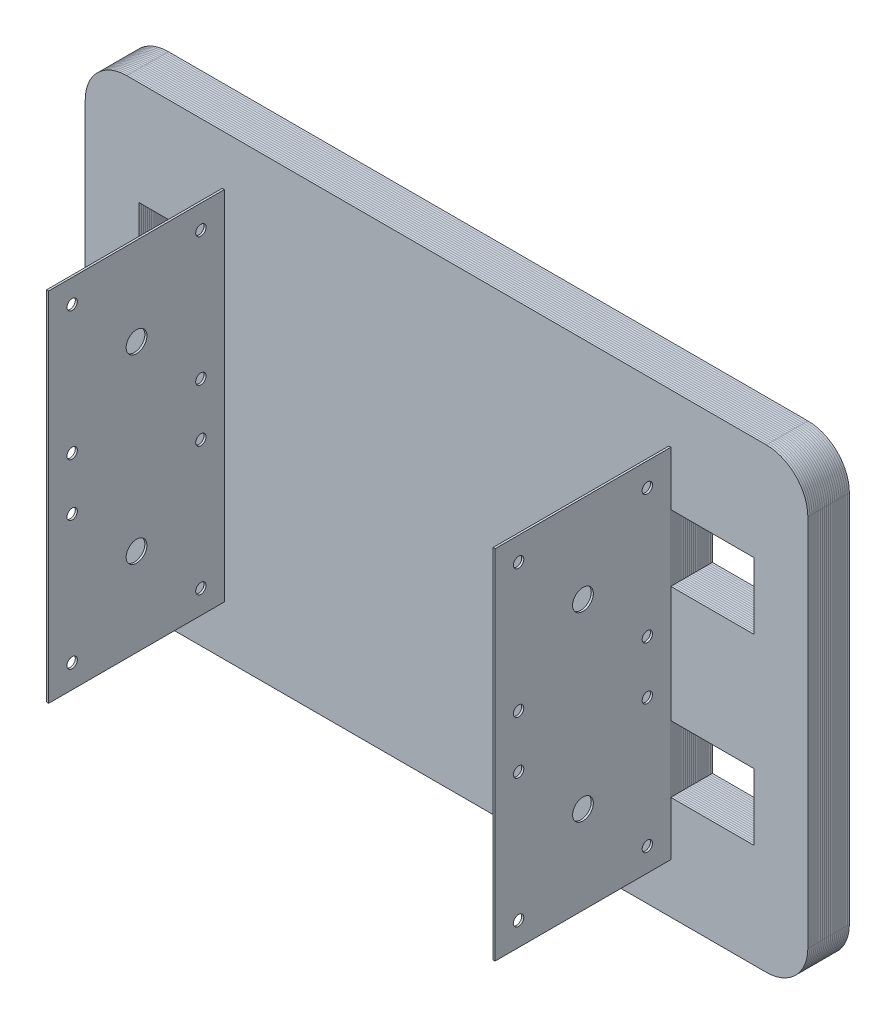
SolidWorks part; units mm, degrees
other "Item de detalhe5"
other "Item de detalhe6"
other "Item de detalhe8"
other "Pasta de soldas"
other "Cordão de solda...1"
other "Cordão de solda...2"
other "Cordão de solda...4"
other "Marcação1"
sketch "Esboço44" plane through (-174, 0, -8.5) normal (-1, 0, 0) x (0, 0, 1)
material "AISI 304"
ref_plane "Plano frontal" through (0, 0, 0) normal (0, 0, 1) x (1, 0, 0)
ref_plane "Plano superior" through (0, 0, 0) normal (0, 1, 0) x (1, 0, 0)
ref_plane "Plano direito" through (0, 0, 0) normal (1, 0, 0) x (0, 0, -1)
sketch "Esboço2" plane through (0, 0, 0) normal (0, 0, 1) x (1, 0, 0)
  line L22 (-10, 0) -> (-164, 0)
  line L23 (0, 10) -> (0, 100)
  line L24 (-10, 110) -> (-164, 110)
  line L25 (-174, 10) -> (-174, 100)
  line L26 (-33.5, 98) -> (-33, 98)
  line L27 (-161, 85) -> (-141, 85)
  line L28 (-161, 85) -> (-161, 69)
  line L29 (-161, 69) -> (-141, 69)
  line L30 (-141, 85) -> (-141, 69)
  line L31 (-33, 85) -> (-13, 85)
  line L32 (-33, 85) -> (-33, 69)
  line L33 (-33, 69) -> (-13, 69)
  line L34 (-13, 85) -> (-13, 69)
  line L35 (-161, 41) -> (-141, 41)
  line L36 (-161, 41) -> (-161, 25)
  line L37 (-161, 25) -> (-141, 25)
  line L38 (-141, 41) -> (-141, 25)
  line L39 (-33, 41) -> (-13, 41)
  line L40 (-33, 41) -> (-33, 25)
  line L41 (-33, 25) -> (-13, 25)
  line L42 (-13, 41) -> (-13, 25)
  line L50 (-140.5, 12) -> (-141, 12)
  line L54 (-33, 12) -> (-33.5, 12)
  line L55 (-33, 12) -> (-33, 98)
  line L59 (-140.5, 98) -> (-140.5, 12)
  line L60 (-33.5, 98) -> (-33.5, 12)
  line L61 (-140.5, 98) -> (-141, 98)
  line L62 (-141, 98) -> (-141, 12)
  arc A4 (-164, 0) -> (-174, 10) centre (-164, 10) cw
  arc A5 (-10, 0) -> (0, 10) centre (-10, 10) ccw
  arc A6 (0, 100) -> (-10, 110) centre (-10, 100) ccw
  arc A7 (-164, 110) -> (-174, 100) centre (-164, 100) ccw
  point P7 (-174, 0)
  point P10 (0, 0)
  point P13 (0, 110)
  point P16 (-174, 110)
  point P37 (-33, 55)
  dimension "D3" = 10
  dimension "D1" = 110
  dimension "D2" = 174
  dimension "D4" = 20
  dimension "D5" = 16
  dimension "D6" = 13
  dimension "D7" = 25
  dimension "D8" = 13
  dimension "D9" = 25
  dimension "D10" = 86
  dimension "D11" = 0.5
  dimension "D12" = 14
extrude "Ressalto-extrusão8" add sketch "Esboço2" against normal blind 0.5 contours L24 A7 L25 A4 L22 A5 L23 A6 L54 L40 L39 L42 L41 L61 L30 L29 L28 L27 L26 L32 L31 L34 L33 L50 L38 L37 L36 L35 | L61 L30 | L38 L50 | L32 L26 | L54 L40 region at (-87, 55, 0) region at (-33.25, 55, 0) region at (-140.75, 55, 0)
extrude "Ressalto-extrusão9" add sketch "Esboço2<13>" along normal blind 42.3 separate body contours L61 L62 L30 L38 L50 L59 | L26 L60 L54 L55 L40 L32 region at (-33.25, 55, 0) region at (-140.75, 55, 0)
sketch "Esboço2<13>" plane through (0, 0, 0) normal (0, 0, 1) x (1, 0, 0) same geometry as "Esboço2"
hole_wizard "Broca de rosquear para tarraxa de M3x0.51" positions "Esboço25" profile "Esboço26" hole size "M3x0.5" standard "Ansi Metric"
sketch "Esboço25" plane through (-141, 0, 0) normal (-1, 0, 0) x (0, 0, 1)
  line L0 (42.3, 98) -> (0, 98) construction
  line L1 (42.3, 98) -> (42.3, 12) construction
  line L2 (42.3, 12) -> (0, 12) construction
  point P0 (36.65, 92.35)
  point P2 (5.65, 92.35)
  point P4 (5.65, 61.35)
  point P6 (36.65, 61.35)
  point P8 (5.65, 48.65)
  point P10 (36.65, 48.65)
  point P12 (36.65, 17.65)
  point P14 (5.65, 17.65)
  dimension "D1" = 31
  dimension "D2" = 31
  dimension "D3" = 5.65
  dimension "D4" = 5.65
  dimension "D5" = 5.65
  dimension "D6" = 31
sketch "Esboço26" plane through (-141, 92.35, 36.65) normal (0, 1, 0) x (0, 0, 1)
  line L0 (0, 0) -> (0, 25.4)
  line L1 (0, 25.4) -> (1.25, 24.6489)
  line L2 (1.25, 24.6489) -> (1.25, 0)
  line L5 (1.25, 0) -> (0, 0)
  line L10 (0, 25.4) -> (-1.25, 24.6489) construction
  line L11 (0, -6.35) -> (0, 107.95) construction
  dimension "Hole Dia." = 2.5
  dimension "Hole Depth" = 25.4
  dimension "Drill Angle" = 118
sketch "Esboço27" plane through (-141, 0, 0) normal (-1, 0, 0) x (0, 0, 1)
  circle A0 centre (5.65, 92.35) radius 1.25
  circle A1 centre (36.65, 92.35) radius 1.25
  circle A2 centre (5.65, 61.35) radius 1.25
  circle A3 centre (36.65, 61.35) radius 1.25
  circle A4 centre (5.65, 48.65) radius 1.25
  circle A5 centre (36.65, 48.65) radius 1.25
  circle A6 centre (5.65, 17.65) radius 1.25
  circle A7 centre (36.65, 17.65) radius 1.25
  circle A8 centre (21.15, 76.85) radius 2.5
  circle A9 centre (21.15, 33.15) radius 2.5
  dimension "D1" = 5
  dimension "D2" = 15.5
  dimension "D3" = 15.5
  dimension "32/2" = 15.5
  dimension "D4" = 15.5
extrude "Corte-extrusão2" cut sketch "Esboço27" against normal through all both and the other way through all
extrude "Corte-extrusão3" cut sketch "Esboço27<2>" against normal through all both and the other way through all
sketch "Esboço27<2>" plane through (-141, 0, 0) normal (-1, 0, 0) x (0, 0, 1) same geometry as "Esboço27"
sketch "Esboço28" plane through (0, 0, -0.5) normal (0, 0, -1) x (-1, 0, 0)
  line L0 (10, 110) -> (164, 110)
  line L1 (174, 100) -> (174, 10)
  line L2 (164, 0) -> (10, 0)
  line L3 (10, 0) -> (164, 0) construction
  line L4 (0, 10) -> (0, 100)
  line L5 (161, 41) -> (161, 25) construction
  line L6 (13, 85) -> (33, 85)
  line L7 (13, 85) -> (13, 69)
  line L8 (13, 69) -> (33, 69)
  line L9 (33, 85) -> (33, 69)
  line L10 (13, 41) -> (33, 41)
  line L11 (13, 41) -> (13, 25)
  line L12 (13, 25) -> (33, 25)
  line L13 (33, 41) -> (33, 25)
  line L14 (141, 85) -> (161, 85)
  line L15 (141, 85) -> (141, 69)
  line L16 (141, 69) -> (161, 69)
  line L17 (161, 85) -> (161, 69)
  line L18 (141, 41) -> (161, 41)
  line L19 (141, 41) -> (141, 25)
  line L20 (141, 25) -> (161, 25)
  line L21 (161, 41) -> (161, 25)
  arc A0 (164, 0) -> (174, 10) centre (164, 10) ccw construction
  arc A1 (0, 100) -> (10, 110) centre (10, 100) cw
  arc A2 (10, 110) -> (0, 100) centre (10, 100) ccw construction
  arc A3 (164, 110) -> (174, 100) centre (164, 100) cw
  arc A4 (174, 100) -> (164, 110) centre (164, 100) ccw construction
  arc A5 (10, 0) -> (0, 10) centre (10, 10) cw
  arc A7 (174, 10) -> (164, 0) centre (164, 10) cw
  arc A8 (0, 10) -> (10, 0) centre (10, 10) ccw construction
extrude "Ressalto-extrusão10" add sketch "Esboço28" along normal blind 0.5 separate body
sketch "Esboço29" plane through (0, 0, -1) normal (0, 0, -1) x (-1, 0, 0)
  line L0 (10, 110) -> (164, 110)
  line L1 (174, 100) -> (174, 10)
  line L2 (10, 0) -> (164, 0)
  line L3 (0, 10) -> (0, 100)
  line L5 (13, 85) -> (33, 85)
  line L6 (13, 85) -> (13, 69)
  line L7 (13, 69) -> (33, 69)
  line L8 (33, 85) -> (33, 69)
  line L9 (13, 41) -> (33, 41)
  line L10 (13, 41) -> (13, 25)
  line L11 (13, 25) -> (33, 25)
  line L12 (33, 41) -> (33, 25)
  line L13 (141, 85) -> (161, 85)
  line L14 (141, 85) -> (141, 69)
  line L15 (141, 69) -> (161, 69)
  line L16 (161, 85) -> (161, 69)
  line L17 (141, 41) -> (161, 41)
  line L18 (141, 41) -> (141, 25)
  line L19 (141, 25) -> (161, 25)
  line L20 (161, 41) -> (161, 25)
  arc A0 (0, 100) -> (10, 110) centre (10, 100) cw
  arc A1 (10, 110) -> (0, 100) centre (10, 100) ccw construction
  arc A2 (164, 110) -> (174, 100) centre (164, 100) cw
  arc A4 (174, 100) -> (164, 110) centre (164, 100) ccw construction
  arc A5 (174, 10) -> (164, 0) centre (164, 10) cw
  arc A6 (164, 0) -> (174, 10) centre (164, 10) ccw construction
  arc A7 (0, 10) -> (10, 0) centre (10, 10) ccw
  arc A8 (0, 10) -> (10, 0) centre (10, 10) ccw construction
extrude "Ressalto-extrusão11" add sketch "Esboço29" along normal blind 0.5 separate body
sketch "Esboço30" plane through (0, 0, -1.5) normal (0, 0, -1) x (-1, 0, 0)
  line L0 (10, 110) -> (164, 110)
  line L1 (174, 100) -> (174, 10)
  line L2 (10, 0) -> (164, 0)
  line L3 (0, 10) -> (0, 100)
  line L4 (13, 85) -> (33, 85)
  line L5 (13, 85) -> (13, 69)
  line L6 (13, 69) -> (33, 69)
  line L7 (33, 85) -> (33, 69)
  line L8 (13, 41) -> (33, 41)
  line L9 (13, 41) -> (13, 25)
  line L10 (13, 25) -> (33, 25)
  line L11 (33, 41) -> (33, 25)
  line L12 (141, 85) -> (161, 85)
  line L13 (141, 85) -> (141, 69)
  line L14 (141, 69) -> (161, 69)
  line L15 (161, 85) -> (161, 69)
  line L16 (141, 41) -> (161, 41)
  line L17 (141, 41) -> (141, 25)
  line L18 (141, 25) -> (161, 25)
  line L19 (161, 41) -> (161, 25)
  line L20 (13, 69) -> (33, 69) construction
  line L21 (13, 85) -> (13, 69) construction
  line L22 (10, 0) -> (164, 0) construction
  line L23 (0, 100) -> (0, 10) construction
  line L24 (164, 110) -> (10, 110) construction
  line L25 (174, 10) -> (174, 100) construction
  line L26 (13, 25) -> (33, 25) construction
  line L28 (161, 25) -> (161, 41) construction
  arc A0 (0, 100) -> (10, 110) centre (10, 100) cw
  arc A1 (164, 110) -> (174, 100) centre (164, 100) cw
  arc A2 (174, 10) -> (164, 0) centre (164, 10) cw
  arc A3 (0, 10) -> (10, 0) centre (10, 10) ccw
extrude "Ressalto-extrusão12" add sketch "Esboço30" along normal blind 0.5 separate body
sketch "Esboço31" plane through (0, 0, -2) normal (0, 0, -1) x (-1, 0, 0)
  line L0 (10, 110) -> (164, 110)
  line L1 (174, 100) -> (174, 10)
  line L2 (10, 0) -> (164, 0)
  line L3 (0, 10) -> (0, 100)
  line L4 (13, 85) -> (33, 85)
  line L5 (13, 85) -> (13, 69)
  line L6 (13, 69) -> (33, 69)
  line L7 (33, 85) -> (33, 69)
  line L8 (13, 41) -> (33, 41)
  line L9 (13, 41) -> (13, 25)
  line L10 (13, 25) -> (33, 25)
  line L11 (33, 41) -> (33, 25)
  line L12 (141, 85) -> (161, 85)
  line L13 (141, 85) -> (141, 69)
  line L14 (141, 69) -> (161, 69)
  line L15 (161, 85) -> (161, 69)
  line L16 (141, 41) -> (161, 41)
  line L17 (141, 41) -> (141, 25)
  line L18 (141, 25) -> (161, 25)
  line L19 (161, 41) -> (161, 25)
  line L20 (10, 0) -> (164, 0) construction
  line L22 (0, 100) -> (0, 10) construction
  line L23 (164, 110) -> (10, 110) construction
  line L24 (174, 10) -> (174, 100) construction
  line L25 (141, 25) -> (161, 25) construction
  line L26 (13, 85) -> (13, 69) construction
  line L27 (161, 69) -> (161, 85) construction
  line L28 (141, 85) -> (141, 69) construction
  line L29 (161, 41) -> (141, 41) construction
  line L30 (161, 85) -> (141, 85) construction
  arc A0 (0, 100) -> (10, 110) centre (10, 100) cw
  arc A1 (164, 110) -> (174, 100) centre (164, 100) cw
  arc A2 (174, 10) -> (164, 0) centre (164, 10) cw
  arc A3 (0, 10) -> (10, 0) centre (10, 10) ccw
extrude "Ressalto-extrusão13" add sketch "Esboço31" along normal blind 0.5 separate body
sketch "Esboço32" plane through (0, 0, -2.5) normal (0, 0, -1) x (-1, 0, 0)
  line L0 (10, 110) -> (164, 110)
  line L1 (174, 100) -> (174, 10)
  line L2 (10, 0) -> (164, 0)
  line L3 (0, 10) -> (0, 100)
  line L4 (13, 85) -> (33, 85)
  line L5 (13, 85) -> (13, 69)
  line L6 (13, 69) -> (33, 69)
  line L7 (33, 85) -> (33, 69)
  line L8 (13, 41) -> (33, 41)
  line L9 (13, 41) -> (13, 25)
  line L10 (13, 25) -> (33, 25)
  line L11 (33, 41) -> (33, 25)
  line L12 (141, 85) -> (161, 85)
  line L13 (141, 85) -> (141, 69)
  line L14 (141, 69) -> (161, 69)
  line L15 (161, 85) -> (161, 69)
  line L16 (141, 41) -> (161, 41)
  line L17 (141, 41) -> (141, 25)
  line L18 (141, 25) -> (161, 25)
  line L19 (161, 41) -> (161, 25)
  line L20 (141, 25) -> (161, 25) construction
  line L21 (13, 41) -> (13, 25) construction
  line L23 (33, 25) -> (33, 41) construction
  line L24 (161, 41) -> (141, 41) construction
  line L26 (161, 69) -> (161, 85) construction
  line L27 (33, 85) -> (13, 85) construction
  arc A0 (0, 100) -> (10, 110) centre (10, 100) cw
  arc A1 (164, 110) -> (174, 100) centre (164, 100) cw
  arc A2 (174, 10) -> (164, 0) centre (164, 10) cw
  arc A3 (0, 10) -> (10, 0) centre (10, 10) ccw
  arc A4 (0, 10) -> (10, 0) centre (10, 10) ccw construction
  arc A5 (10, 110) -> (0, 100) centre (10, 100) ccw construction
  arc A6 (174, 100) -> (164, 110) centre (164, 100) ccw construction
extrude "Ressalto-extrusão14" add sketch "Esboço32" along normal blind 0.5 separate body
sketch "Esboço33" plane through (0, 0, -3) normal (0, 0, -1) x (-1, 0, 0)
  line L0 (10, 110) -> (164, 110)
  line L1 (174, 100) -> (174, 10)
  line L2 (10, 0) -> (164, 0)
  line L3 (0, 10) -> (0, 100)
  line L4 (13, 85) -> (33, 85)
  line L5 (13, 85) -> (13, 69)
  line L6 (13, 69) -> (33, 69)
  line L7 (33, 85) -> (33, 69)
  line L8 (13, 41) -> (33, 41)
  line L9 (13, 41) -> (13, 25)
  line L10 (13, 25) -> (33, 25)
  line L11 (33, 41) -> (33, 25)
  line L12 (141, 85) -> (161, 85)
  line L13 (141, 85) -> (141, 69)
  line L14 (141, 69) -> (161, 69)
  line L15 (161, 85) -> (161, 69)
  line L16 (141, 41) -> (161, 41)
  line L17 (141, 41) -> (141, 25)
  line L18 (141, 25) -> (161, 25)
  line L19 (161, 41) -> (161, 25)
  line L20 (0, 100) -> (0, 10) construction
  line L21 (161, 69) -> (161, 85) construction
  line L22 (141, 69) -> (161, 69) construction
  line L23 (141, 25) -> (161, 25) construction
  line L24 (161, 41) -> (141, 41) construction
  line L25 (13, 85) -> (13, 69) construction
  line L26 (33, 69) -> (33, 85) construction
  arc A0 (0, 100) -> (10, 110) centre (10, 100) cw
  arc A1 (164, 110) -> (174, 100) centre (164, 100) cw
  arc A2 (174, 10) -> (164, 0) centre (164, 10) cw
  arc A3 (0, 10) -> (10, 0) centre (10, 10) ccw
  arc A5 (0, 10) -> (10, 0) centre (10, 10) ccw construction
  arc A6 (174, 100) -> (164, 110) centre (164, 100) ccw construction
extrude "Ressalto-extrusão15" add sketch "Esboço33" along normal blind 0.5 separate body
sketch "Esboço34" plane through (0, 0, -3.5) normal (0, 0, -1) x (-1, 0, 0)
  line L0 (10, 110) -> (164, 110)
  line L1 (174, 100) -> (174, 10)
  line L2 (10, 0) -> (164, 0)
  line L3 (0, 10) -> (0, 100)
  line L4 (13, 85) -> (33, 85)
  line L5 (13, 85) -> (13, 69)
  line L6 (13, 69) -> (33, 69)
  line L7 (33, 85) -> (33, 69)
  line L8 (13, 41) -> (33, 41)
  line L9 (13, 41) -> (13, 25)
  line L10 (13, 25) -> (33, 25)
  line L11 (33, 41) -> (33, 25)
  line L12 (141, 85) -> (161, 85)
  line L13 (141, 85) -> (141, 69)
  line L14 (141, 69) -> (161, 69)
  line L15 (161, 85) -> (161, 69)
  line L16 (141, 41) -> (161, 41)
  line L17 (141, 41) -> (141, 25)
  line L18 (141, 25) -> (161, 25)
  line L19 (161, 41) -> (161, 25)
  line L20 (0, 100) -> (0, 10) construction
  line L21 (33, 41) -> (13, 41) construction
  arc A0 (0, 100) -> (10, 110) centre (10, 100) cw
  arc A1 (164, 110) -> (174, 100) centre (164, 100) cw
  arc A2 (174, 10) -> (164, 0) centre (164, 10) cw
  arc A3 (0, 10) -> (10, 0) centre (10, 10) ccw
  arc A4 (164, 0) -> (174, 10) centre (164, 10) ccw construction
  arc A5 (174, 100) -> (164, 110) centre (164, 100) ccw construction
  arc A6 (0, 10) -> (10, 0) centre (10, 10) ccw construction
extrude "Ressalto-extrusão16" add sketch "Esboço34" along normal blind 0.5 separate body
sketch "Esboço35" plane through (0, 0, -4) normal (0, 0, -1) x (-1, 0, 0)
  line L0 (10, 110) -> (164, 110)
  line L1 (174, 100) -> (174, 10)
  line L2 (10, 0) -> (164, 0)
  line L3 (0, 10) -> (0, 100)
  line L4 (13, 85) -> (33, 85)
  line L5 (13, 85) -> (13, 69)
  line L6 (13, 69) -> (33, 69)
  line L7 (33, 85) -> (33, 69)
  line L8 (13, 41) -> (33, 41)
  line L9 (13, 41) -> (13, 25)
  line L10 (13, 25) -> (33, 25)
  line L11 (33, 41) -> (33, 25)
  line L12 (141, 85) -> (161, 85)
  line L13 (141, 85) -> (141, 69)
  line L14 (141, 69) -> (161, 69)
  line L15 (161, 85) -> (161, 69)
  line L16 (141, 41) -> (161, 41)
  line L17 (141, 41) -> (141, 25)
  line L18 (141, 25) -> (161, 25)
  line L19 (161, 41) -> (161, 25)
  line L20 (0, 100) -> (0, 10) construction
  arc A0 (0, 100) -> (10, 110) centre (10, 100) cw
  arc A1 (164, 110) -> (174, 100) centre (164, 100) cw
  arc A2 (174, 10) -> (164, 0) centre (164, 10) cw
  arc A3 (0, 10) -> (10, 0) centre (10, 10) ccw
  arc A4 (0, 10) -> (10, 0) centre (10, 10) ccw construction
  arc A6 (174, 100) -> (164, 110) centre (164, 100) ccw construction
extrude "Ressalto-extrusão17" add sketch "Esboço35" along normal blind 0.5 separate body
sketch "Esboço36" plane through (0, 0, -4.5) normal (0, 0, -1) x (-1, 0, 0)
  line L0 (10, 110) -> (164, 110)
  line L1 (174, 100) -> (174, 10)
  line L2 (10, 0) -> (164, 0)
  line L3 (0, 10) -> (0, 100)
  line L4 (13, 85) -> (33, 85)
  line L5 (13, 85) -> (13, 69)
  line L6 (13, 69) -> (33, 69)
  line L7 (33, 85) -> (33, 69)
  line L8 (13, 41) -> (33, 41)
  line L9 (13, 41) -> (13, 25)
  line L10 (13, 25) -> (33, 25)
  line L11 (33, 41) -> (33, 25)
  line L12 (141, 85) -> (161, 85)
  line L13 (141, 85) -> (141, 69)
  line L14 (141, 69) -> (161, 69)
  line L15 (161, 85) -> (161, 69)
  line L16 (141, 41) -> (161, 41)
  line L17 (141, 41) -> (141, 25)
  line L18 (141, 25) -> (161, 25)
  line L19 (161, 41) -> (161, 25)
  line L20 (13, 25) -> (33, 25) construction
  line L21 (141, 85) -> (141, 69) construction
  arc A0 (0, 100) -> (10, 110) centre (10, 100) cw
  arc A1 (164, 110) -> (174, 100) centre (164, 100) cw
  arc A2 (174, 10) -> (164, 0) centre (164, 10) cw
  arc A3 (0, 10) -> (10, 0) centre (10, 10) ccw
  arc A4 (10, 110) -> (0, 100) centre (10, 100) ccw construction
  arc A5 (164, 0) -> (174, 10) centre (164, 10) ccw construction
  arc A6 (0, 10) -> (10, 0) centre (10, 10) ccw construction
extrude "Ressalto-extrusão18" add sketch "Esboço36" along normal blind 0.5 separate body
sketch "Esboço37" plane through (0, 0, -5) normal (0, 0, -1) x (-1, 0, 0)
  line L0 (10, 110) -> (164, 110)
  line L1 (174, 100) -> (174, 10)
  line L2 (10, 0) -> (164, 0)
  line L3 (0, 10) -> (0, 100)
  line L4 (13, 85) -> (33, 85)
  line L5 (13, 85) -> (13, 69)
  line L6 (13, 69) -> (33, 69)
  line L7 (33, 85) -> (33, 69)
  line L8 (13, 41) -> (33, 41)
  line L9 (13, 41) -> (13, 25)
  line L10 (13, 25) -> (33, 25)
  line L11 (33, 41) -> (33, 25)
  line L12 (141, 85) -> (161, 85)
  line L13 (141, 85) -> (141, 69)
  line L14 (141, 69) -> (161, 69)
  line L15 (161, 85) -> (161, 69)
  line L16 (141, 41) -> (161, 41)
  line L17 (141, 41) -> (141, 25)
  line L18 (141, 25) -> (161, 25)
  line L19 (161, 41) -> (161, 25)
  line L20 (10, 0) -> (164, 0) construction
  line L21 (0, 100) -> (0, 10) construction
  arc A0 (0, 100) -> (10, 110) centre (10, 100) cw
  arc A1 (164, 110) -> (174, 100) centre (164, 100) cw
  arc A2 (174, 10) -> (164, 0) centre (164, 10) cw
  arc A3 (0, 10) -> (10, 0) centre (10, 10) ccw
  arc A4 (174, 100) -> (164, 110) centre (164, 100) ccw construction
  arc A5 (0, 10) -> (10, 0) centre (10, 10) ccw construction
extrude "Ressalto-extrusão19" add sketch "Esboço37" along normal blind 0.5 separate body
sketch "Esboço38" plane through (0, 0, -5.5) normal (0, 0, -1) x (-1, 0, 0)
  line L0 (10, 110) -> (164, 110)
  line L1 (174, 100) -> (174, 10)
  line L2 (10, 0) -> (164, 0)
  line L3 (0, 10) -> (0, 100)
  line L4 (13, 85) -> (33, 85)
  line L5 (13, 85) -> (13, 69)
  line L6 (13, 69) -> (33, 69)
  line L7 (33, 85) -> (33, 69)
  line L8 (13, 41) -> (33, 41)
  line L9 (13, 41) -> (13, 25)
  line L10 (13, 25) -> (33, 25)
  line L11 (33, 41) -> (33, 25)
  line L12 (141, 85) -> (161, 85)
  line L13 (141, 85) -> (141, 69)
  line L14 (141, 69) -> (161, 69)
  line L15 (161, 85) -> (161, 69)
  line L16 (141, 41) -> (161, 41)
  line L17 (141, 41) -> (141, 25)
  line L18 (141, 25) -> (161, 25)
  line L19 (161, 41) -> (161, 25)
  line L20 (10, 0) -> (164, 0) construction
  line L21 (0, 100) -> (0, 10) construction
  arc A0 (0, 100) -> (10, 110) centre (10, 100) cw
  arc A1 (164, 110) -> (174, 100) centre (164, 100) cw
  arc A2 (174, 10) -> (164, 0) centre (164, 10) cw
  arc A3 (0, 10) -> (10, 0) centre (10, 10) ccw
  arc A4 (174, 100) -> (164, 110) centre (164, 100) ccw construction
  arc A5 (0, 10) -> (10, 0) centre (10, 10) ccw construction
extrude "Ressalto-extrusão20" add sketch "Esboço38" along normal blind 0.5 separate body
sketch "Esboço39" plane through (0, 0, -6) normal (0, 0, -1) x (-1, 0, 0)
  line L0 (10, 110) -> (164, 110)
  line L1 (174, 100) -> (174, 10)
  line L2 (10, 0) -> (164, 0)
  line L3 (0, 10) -> (0, 100)
  line L4 (13, 85) -> (33, 85)
  line L5 (13, 85) -> (13, 69)
  line L6 (13, 69) -> (33, 69)
  line L7 (33, 85) -> (33, 69)
  line L8 (13, 41) -> (33, 41)
  line L9 (13, 41) -> (13, 25)
  line L10 (13, 25) -> (33, 25)
  line L11 (33, 41) -> (33, 25)
  line L12 (141, 85) -> (161, 85)
  line L13 (141, 85) -> (141, 69)
  line L14 (141, 69) -> (161, 69)
  line L15 (161, 85) -> (161, 69)
  line L16 (141, 41) -> (161, 41)
  line L17 (141, 41) -> (141, 25)
  line L18 (141, 25) -> (161, 25)
  line L19 (161, 41) -> (161, 25)
  line L21 (10, 0) -> (164, 0) construction
  line L22 (0, 100) -> (0, 10) construction
  arc A0 (0, 100) -> (10, 110) centre (10, 100) cw
  arc A1 (164, 110) -> (174, 100) centre (164, 100) cw
  arc A2 (174, 10) -> (164, 0) centre (164, 10) cw
  arc A3 (0, 10) -> (10, 0) centre (10, 10) ccw
  arc A4 (0, 10) -> (10, 0) centre (10, 10) ccw construction
  arc A5 (174, 100) -> (164, 110) centre (164, 100) ccw construction
extrude "Ressalto-extrusão21" add sketch "Esboço39" along normal blind 0.5 separate body
sketch "Esboço40" plane through (0, 0, -6.5) normal (0, 0, -1) x (-1, 0, 0)
  line L0 (10, 110) -> (164, 110)
  line L1 (174, 100) -> (174, 10)
  line L2 (10, 0) -> (164, 0)
  line L3 (0, 10) -> (0, 100)
  line L4 (13, 85) -> (33, 85)
  line L5 (13, 85) -> (13, 69)
  line L6 (13, 69) -> (33, 69)
  line L7 (33, 85) -> (33, 69)
  line L8 (13, 41) -> (33, 41)
  line L9 (13, 41) -> (13, 25)
  line L10 (13, 25) -> (33, 25)
  line L11 (33, 41) -> (33, 25)
  line L12 (141, 85) -> (161, 85)
  line L13 (141, 85) -> (141, 69)
  line L14 (141, 69) -> (161, 69)
  line L15 (161, 85) -> (161, 69)
  line L16 (141, 41) -> (161, 41)
  line L17 (141, 41) -> (141, 25)
  line L18 (141, 25) -> (161, 25)
  line L19 (161, 41) -> (161, 25)
  line L20 (10, 0) -> (164, 0) construction
  line L21 (174, 10) -> (174, 100) construction
  arc A0 (0, 100) -> (10, 110) centre (10, 100) cw
  arc A1 (164, 110) -> (174, 100) centre (164, 100) cw
  arc A2 (174, 10) -> (164, 0) centre (164, 10) cw
  arc A3 (0, 10) -> (10, 0) centre (10, 10) ccw
  arc A4 (0, 10) -> (10, 0) centre (10, 10) ccw construction
  arc A5 (174, 100) -> (164, 110) centre (164, 100) ccw construction
extrude "Ressalto-extrusão22" add sketch "Esboço40" along normal blind 0.5 separate body
sketch "Esboço41" plane through (0, 0, -7) normal (0, 0, -1) x (-1, 0, 0)
  line L0 (10, 110) -> (164, 110)
  line L1 (174, 100) -> (174, 10)
  line L2 (10, 0) -> (164, 0)
  line L3 (0, 10) -> (0, 100)
  line L4 (13, 85) -> (33, 85)
  line L5 (13, 85) -> (13, 69)
  line L6 (13, 69) -> (33, 69)
  line L7 (33, 85) -> (33, 69)
  line L8 (13, 41) -> (33, 41)
  line L9 (13, 41) -> (13, 25)
  line L10 (13, 25) -> (33, 25)
  line L11 (33, 41) -> (33, 25)
  line L12 (141, 85) -> (161, 85)
  line L13 (141, 85) -> (141, 69)
  line L14 (141, 69) -> (161, 69)
  line L15 (161, 85) -> (161, 69)
  line L16 (141, 41) -> (161, 41)
  line L17 (141, 41) -> (141, 25)
  line L18 (141, 25) -> (161, 25)
  line L19 (161, 41) -> (161, 25)
  line L20 (164, 110) -> (10, 110) construction
  line L21 (0, 100) -> (0, 10) construction
  line L22 (174, 10) -> (174, 100) construction
  arc A0 (0, 100) -> (10, 110) centre (10, 100) cw
  arc A1 (164, 110) -> (174, 100) centre (164, 100) cw
  arc A2 (174, 10) -> (164, 0) centre (164, 10) cw
  arc A3 (0, 10) -> (10, 0) centre (10, 10) ccw
  arc A4 (10, 110) -> (0, 100) centre (10, 100) ccw construction
  arc A5 (0, 10) -> (10, 0) centre (10, 10) ccw construction
  arc A6 (164, 0) -> (174, 10) centre (164, 10) ccw construction
extrude "Ressalto-extrusão23" add sketch "Esboço41" along normal blind 0.5 separate body
sketch "Esboço42" plane through (0, 0, -7.5) normal (0, 0, -1) x (-1, 0, 0)
  line L0 (10, 110) -> (164, 110)
  line L1 (174, 100) -> (174, 10)
  line L2 (10, 0) -> (164, 0)
  line L3 (0, 10) -> (0, 100)
  line L4 (13, 85) -> (33, 85)
  line L5 (13, 85) -> (13, 69)
  line L6 (13, 69) -> (33, 69)
  line L7 (33, 85) -> (33, 69)
  line L8 (13, 41) -> (33, 41)
  line L9 (13, 41) -> (13, 25)
  line L10 (13, 25) -> (33, 25)
  line L11 (33, 41) -> (33, 25)
  line L12 (141, 85) -> (161, 85)
  line L13 (141, 85) -> (141, 69)
  line L14 (141, 69) -> (161, 69)
  line L15 (161, 85) -> (161, 69)
  line L16 (141, 41) -> (161, 41)
  line L17 (141, 41) -> (141, 25)
  line L18 (141, 25) -> (161, 25)
  line L19 (161, 41) -> (161, 25)
  line L20 (10, 0) -> (164, 0) construction
  line L21 (0, 100) -> (0, 10) construction
  line L22 (174, 10) -> (174, 100) construction
  arc A0 (0, 100) -> (10, 110) centre (10, 100) cw
  arc A1 (164, 110) -> (174, 100) centre (164, 100) cw
  arc A2 (174, 10) -> (164, 0) centre (164, 10) cw
  arc A3 (0, 10) -> (10, 0) centre (10, 10) ccw
  arc A4 (174, 100) -> (164, 110) centre (164, 100) ccw construction
extrude "Ressalto-extrusão24" add sketch "Esboço42" along normal blind 0.5 separate body
sketch "Esboço43" plane through (0, 0, -8) normal (0, 0, -1) x (-1, 0, 0)
  line L0 (10, 110) -> (164, 110)
  line L1 (174, 100) -> (174, 10)
  line L2 (10, 0) -> (164, 0)
  line L3 (0, 10) -> (0, 100)
  line L4 (13, 85) -> (33, 85)
  line L5 (13, 85) -> (13, 69)
  line L6 (13, 69) -> (33, 69)
  line L7 (33, 85) -> (33, 69)
  line L8 (13, 41) -> (33, 41)
  line L9 (13, 41) -> (13, 25)
  line L10 (13, 25) -> (33, 25)
  line L11 (33, 41) -> (33, 25)
  line L12 (141, 85) -> (161, 85)
  line L13 (141, 85) -> (141, 69)
  line L14 (141, 69) -> (161, 69)
  line L15 (161, 85) -> (161, 69)
  line L16 (141, 41) -> (161, 41)
  line L17 (141, 41) -> (141, 25)
  line L18 (141, 25) -> (161, 25)
  line L19 (161, 41) -> (161, 25)
  line L20 (10, 0) -> (164, 0) construction
  line L21 (0, 100) -> (0, 10) construction
  arc A0 (0, 100) -> (10, 110) centre (10, 100) cw
  arc A1 (164, 110) -> (174, 100) centre (164, 100) cw
  arc A2 (174, 10) -> (164, 0) centre (164, 10) cw
  arc A3 (0, 10) -> (10, 0) centre (10, 10) ccw
  arc A4 (174, 100) -> (164, 110) centre (164, 100) ccw construction
  arc A5 (0, 10) -> (10, 0) centre (10, 10) ccw construction
extrude "Ressalto-extrusão25" add sketch "Esboço43" along normal blind 0.5 separate body
sketch "Esboço46" plane through (0, 0, -8.5) normal (0, 0, -1) x (-1, 0, 0)
  line L0 (10, 110) -> (164, 110)
  line L1 (174, 100) -> (174, 10)
  line L2 (10, 0) -> (164, 0)
  line L3 (0, 10) -> (0, 100)
  line L4 (13, 85) -> (33, 85)
  line L5 (13, 85) -> (13, 69)
  line L6 (13, 69) -> (33, 69)
  line L7 (33, 85) -> (33, 69)
  line L8 (13, 41) -> (33, 41)
  line L9 (13, 41) -> (13, 25)
  line L10 (13, 25) -> (33, 25)
  line L11 (33, 41) -> (33, 25)
  line L12 (141, 85) -> (161, 85)
  line L13 (141, 85) -> (141, 69)
  line L14 (141, 69) -> (161, 69)
  line L15 (161, 85) -> (161, 69)
  line L16 (141, 41) -> (161, 41)
  line L17 (141, 41) -> (141, 25)
  line L18 (141, 25) -> (161, 25)
  line L19 (161, 41) -> (161, 25)
  line L21 (10, 0) -> (164, 0) construction
  line L22 (174, 10) -> (174, 100) construction
  arc A0 (0, 100) -> (10, 110) centre (10, 100) cw
  arc A1 (164, 110) -> (174, 100) centre (164, 100) cw
  arc A2 (174, 10) -> (164, 0) centre (164, 10) cw
  arc A3 (0, 10) -> (10, 0) centre (10, 10) ccw
  arc A4 (164, 0) -> (174, 10) centre (164, 10) ccw construction
  arc A7 (10, 110) -> (0, 100) centre (10, 100) ccw construction
  arc A8 (174, 100) -> (164, 110) centre (164, 100) ccw construction
extrude "Ressalto-extrusão27" add sketch "Esboço46" along normal blind 0.5 separate body
sketch "Esboço47" plane through (0, 0, -9) normal (0, 0, -1) x (-1, 0, 0)
  line L0 (10, 110) -> (164, 110)
  line L1 (174, 100) -> (174, 10)
  line L2 (10, 0) -> (164, 0)
  line L3 (0, 10) -> (0, 100)
  line L4 (13, 85) -> (33, 85)
  line L5 (13, 85) -> (13, 69)
  line L6 (13, 69) -> (33, 69)
  line L7 (33, 85) -> (33, 69)
  line L8 (13, 41) -> (33, 41)
  line L9 (13, 41) -> (13, 25)
  line L10 (13, 25) -> (33, 25)
  line L11 (33, 41) -> (33, 25)
  line L12 (141, 85) -> (161, 85)
  line L13 (141, 85) -> (141, 69)
  line L14 (141, 69) -> (161, 69)
  line L15 (161, 85) -> (161, 69)
  line L16 (141, 41) -> (161, 41)
  line L17 (141, 41) -> (141, 25)
  line L18 (141, 25) -> (161, 25)
  line L19 (161, 41) -> (161, 25)
  line L20 (164, 110) -> (10, 110) construction
  line L21 (0, 100) -> (0, 10) construction
  arc A0 (0, 100) -> (10, 110) centre (10, 100) cw
  arc A1 (164, 110) -> (174, 100) centre (164, 100) cw
  arc A2 (174, 10) -> (164, 0) centre (164, 10) cw
  arc A3 (0, 10) -> (10, 0) centre (10, 10) ccw
  arc A4 (0, 10) -> (10, 0) centre (10, 10) ccw construction
  arc A5 (174, 100) -> (164, 110) centre (164, 100) ccw construction
extrude "Ressalto-extrusão28" add sketch "Esboço47" along normal blind 0.5 separate body
sketch "Esboço48" plane through (0, 0, -9.5) normal (0, 0, -1) x (-1, 0, 0)
  line L0 (10, 110) -> (164, 110)
  line L1 (174, 100) -> (174, 10)
  line L2 (10, 0) -> (164, 0)
  line L3 (0, 10) -> (0, 100)
  line L4 (13, 85) -> (33, 85)
  line L5 (13, 85) -> (13, 69)
  line L6 (13, 69) -> (33, 69)
  line L7 (33, 85) -> (33, 69)
  line L8 (13, 41) -> (33, 41)
  line L9 (13, 41) -> (13, 25)
  line L10 (13, 25) -> (33, 25)
  line L11 (33, 41) -> (33, 25)
  line L12 (141, 85) -> (161, 85)
  line L13 (141, 85) -> (141, 69)
  line L14 (141, 69) -> (161, 69)
  line L15 (161, 85) -> (161, 69)
  line L16 (141, 41) -> (161, 41)
  line L17 (141, 41) -> (141, 25)
  line L18 (141, 25) -> (161, 25)
  line L19 (161, 41) -> (161, 25)
  line L20 (174, 10) -> (174, 100) construction
  line L21 (10, 0) -> (164, 0) construction
  arc A0 (0, 100) -> (10, 110) centre (10, 100) cw
  arc A1 (164, 110) -> (174, 100) centre (164, 100) cw
  arc A2 (174, 10) -> (164, 0) centre (164, 10) cw
  arc A3 (0, 10) -> (10, 0) centre (10, 10) ccw
  arc A4 (164, 0) -> (174, 10) centre (164, 10) ccw construction
  arc A5 (10, 110) -> (0, 100) centre (10, 100) ccw construction
  arc A6 (174, 100) -> (164, 110) centre (164, 100) ccw construction
extrude "Ressalto-extrusão30" add sketch "Esboço48" along normal blind 0.5 separate body
